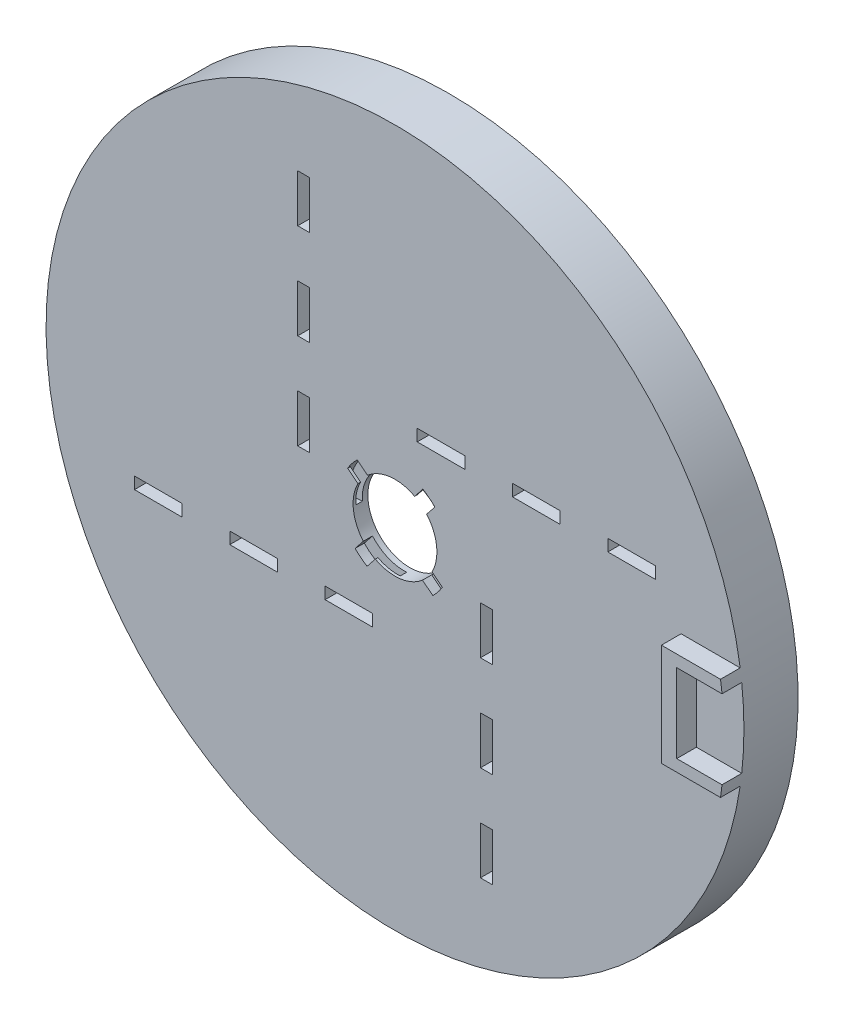
SolidWorks part; units mm, degrees
material "ABS"
ref_plane "Front Plane" through (0, 0, 0) normal (0, 0, 1) x (1, 0, 0)
ref_plane "Top Plane" through (0, 0, 0) normal (0, 1, 0) x (1, 0, 0)
ref_plane "Right Plane" through (0, 0, 0) normal (1, 0, 0) x (0, 0, -1)
sketch "Sketch1" plane through (0, 0, 0) normal (0, 0, 1) x (1, 0, 0)
  line L0 (0, 0) -> (0, -100) construction
  line L1 (-100, -100) -> (100, -100)
  line L2 (-100, -100) -> (-100, 100)
  line L3 (100, -100) -> (100, 100)
  line L4 (100, 100) -> (-100, 100)
  circle A0 centre (0, 0) radius 10.65
  point P7 (0, -100)
  dimension "D1" = 21.3
  dimension "D2" = 100
  dimension "D3" = 200
  dimension "D4" = 200
extrude "Boss-Extrude1" add sketch "Sketch1" against normal blind 3.75
sketch "Sketch2" plane through (0, 0, 0) normal (0, 0, 1) x (1, 0, 0)
  line L0 (0, 0) -> (0, 13.95) construction
  line L1 (0, 10.65) -> (0, 13.95)
  line L2 (8.6829, 10.9183) -> (6.6289, 8.3355)
  line L3 (-0.8501, 13.9241) -> (-0.649, 10.6302)
  circle A0 centre (0, 0) radius 10.65 construction
  circle A1 centre (0, 0) radius 13.95
  circle A2 centre (0, 0) radius 10.65
  arc A3 (0, 12.3) -> (-0.7495, 12.2771) centre (0, 0) ccw construction
  arc A4 (0, 12.3) -> (0.7495, 12.2771) centre (0, 0) cw construction
  arc A5 (0.7495, 12.2771) -> (7.6559, 9.6269) centre (0, 0) cw construction
  arc A6 (0.8501, 13.9241) -> (8.6829, 10.9183) centre (0, 0) cw
  arc A7 (0, 13.95) -> (0.8501, 13.9241) centre (0, 0) cw
  arc A8 (0, 13.95) -> (-0.8501, 13.9241) centre (0, 0) ccw
  arc A9 (0.649, 10.6302) -> (6.6289, 8.3355) centre (0, 0) cw
  arc A10 (0, 10.65) -> (0.649, 10.6302) centre (0, 0) cw
  arc A11 (0, 10.65) -> (-0.649, 10.6302) centre (0, 0) ccw
  dimension "D7" = 21.3
  dimension "D2" = 0.75
  dimension "D3" = 0.75
  dimension "D4" = 35
  dimension "D1" = 3.3
  dimension "D5" = 1.65
  dimension "D6" = 1.65
extrude "Cut-Extrude4" cut sketch "Sketch2" against normal mid plane 1.65 from offset 1.5 contours L2 A9 A10 A11 L3 A8 A7 A6 offset against normal yes
sketch "Sketch4" plane through (0, 0, -2.325) normal (0, 0, 1) x (1, 0, 0)
  line L0 (5.0003, 9.4031) -> (7.0769, 12.0216)
  line L1 (8.0358, 6.9892) -> (10.1194, 9.6021)
  arc A0 (6.6289, 8.3355) -> (8.0358, 6.9892) centre (0, 0) cw
  arc A1 (6.6289, 8.3355) -> (5.0003, 9.4031) centre (0, 0) ccw
  arc A2 (8.6829, 10.9183) -> (7.0769, 12.0216) centre (0, 0) ccw
  arc A3 (8.6829, 10.9183) -> (10.1194, 9.6021) centre (0, 0) cw
  dimension "D1" = 1.95
  dimension "D2" = 1.95
  dimension "D3" = 1.95
  dimension "D4" = 1.95
extrude "Cut-Extrude5" cut sketch "Sketch4" along normal through all
pattern_circular "CirPattern1" count 4 over 360 about axis through (0, 0, 0) along (0, 0, 1) of "Cut-Extrude5", "Cut-Extrude4"
sketch "Sketch5" plane through (0, 0, 0) normal (0, 0, 1) x (1, 0, 0)
  line L0 (0, 0) -> (15, 0)
  line L1 (15, 0) -> (47, 0)
  line L2 (47, 0) -> (15.5, 0)
  line L3 (15.5, 0) -> (5.65, 0)
  line L4 (5.65, 0) -> (5.65, 21.7)
  line L5 (5.65, 21.7) -> (17.75, 21.7)
  line L6 (5.65, 21.7) -> (5.65, 24.7)
  line L7 (17.75, 21.7) -> (17.75, 24.7)
  line L8 (5.65, 24.7) -> (17.75, 24.7)
  line L9 (17.75, 21.7) -> (29.85, 21.7)
  line L10 (29.85, 21.7) -> (29.85, 24.7)
  line L11 (29.85, 21.7) -> (41.95, 21.7)
  line L12 (29.85, 24.7) -> (41.95, 24.7)
  line L13 (41.95, 21.7) -> (41.95, 24.7)
  line L14 (41.95, 21.7) -> (54.05, 21.7)
  line L15 (54.05, 21.7) -> (66.15, 21.7)
  line L16 (54.05, 21.7) -> (54.05, 24.7)
  line L17 (66.15, 21.7) -> (66.15, 24.7)
  line L18 (54.05, 24.7) -> (66.15, 24.7)
  dimension "D1" = 15
  dimension "D2" = 32
  dimension "D3" = 31.5
  dimension "D4" = 9.85
  dimension "D5" = 21.7
  dimension "D6" = 12.1
  dimension "D7" = 3
  dimension "D8" = 12.1
  dimension "D9" = 12.1
  dimension "D10" = 12.1
  dimension "D11" = 12.1
  dimension "D12" = 3
  dimension "D13" = 3
extrude "Cut-Extrude6" cut sketch "Sketch5" against normal blind 10 contours L11 L13 L12 L10 | L18 L16 L15 L17 | L5 L6 L8 L7 region at (60.1, 23.2, 0) region at (35.9, 23.2, 0)
pattern_circular "CirPattern2" count 4 over 360 about axis through (0, 0, -3.75) along (0, 0, 1) of "Cut-Extrude6"
sketch "Sketch6" plane through (0, 0, -3.75) normal (0, 0, -1) x (-1, 0, 0)
  line L0 (100, -100) -> (-100, -100)
  line L1 (100, -100) -> (100, 100.1827)
  line L2 (-100, -100) -> (-100, 100.1827)
  line L3 (100, 100.1827) -> (-100, 100.1827)
  circle A0 centre (0, 0) radius 70.611 construction
  circle A1 centre (0, 0) radius 88.611
  dimension "D1" = 18
extrude "Cut-Extrude7" cut sketch "Sketch6" against normal through all contours L0 L1 L3 L2 | A1
sketch "Sketch8" plane through (0, 0, 0) normal (0, 0, 1) x (1, 0, 0)
  line L0 (0, 0) -> (-80.611, 0)
  line L1 (-88.2738, 7.723) -> (-86.7795, 7.5922)
  line L2 (-88.2738, -7.723) -> (-86.7795, -7.5922)
  circle A0 centre (0, 0) radius 88.611 construction
  circle A1 centre (0, 0) radius 87.111 construction
  circle A2 centre (0, 0) radius 86.111
  circle A3 centre (0, 0) radius 84.611
  arc A5 (-88.2738, 7.723) -> (-88.2738, -7.723) centre (0, 0) cw
  arc A6 (-88.2738, 7.723) -> (-88.2738, -7.723) centre (0, 0) ccw construction
  arc A7 (-86.7795, 7.5922) -> (-86.7795, -7.5922) centre (0, 0) cw
  circle A8 centre (0, 0) radius 88.611 construction
  dimension "D4" = 1.5
  dimension "D1" = 1.5
  dimension "D2" = 1
  dimension "D3" = 1.5
extrude "Boss-Extrude2" add sketch "Sketch8" against normal blind 13.75 contours A0 A1 | A2 A3 | L1 A7 L2 A5 region at (-85.8674, 0, 0)
sketch "Sketch9" plane through (0, 0, 0) normal (0, 0, 1) x (1, 0, 0)
  line L0 (0, 0) -> (88.611, 0)
  line L1 (0, 0) -> (83.2671, 30.3067) construction
  circle A0 centre (0, 0) radius 88.611 construction
  dimension "D1" = 20
ref_plane "Plane1" through (83.2671, 0, 0) normal (1, 0, 0) x (0, 0, -1)
sketch "Sketch10" plane through (83.2671, 0, 0) normal (1, 0, 0) x (0, 0, -1)
  line L0 (0, 30.3067) -> (3.75, 30.3067) construction
  circle A0 centre (1.875, 30.3067) radius 0.825
  dimension "D1" = 3.75
  dimension "D2" = 1.65
sketch "Sketch11" plane through (0, 0, 0) normal (0, 0, 1) x (1, 0, 0)
  line L0 (76.546, -10) -> (88.0449, -10)
  line L1 (76.546, -10) -> (88.0449, -10) construction
  line L2 (76.546, 10) -> (76.546, -10) construction
  line L3 (76.546, -10) -> (76.546, 10)
  line L4 (76.546, 10) -> (88.0449, 10)
  line L5 (88.611, 0) -> (0, 0) construction
  line L6 (106.546, -13) -> (87.6522, -13) construction
  line L7 (87.6522, 13) -> (72.6522, 13)
  line L8 (72.6522, 13) -> (72.6522, -13)
  line L9 (72.6522, -13) -> (87.6522, -13)
  arc A0 (88.0449, -10) -> (87.6522, -13) centre (0, 0) cw
  circle A1 centre (0, 0) radius 88.611 construction
  arc A4 (88.0449, 10) -> (87.6522, 13) centre (0, 0) ccw
  dimension "D1" = 15
extrude "Boss-Extrude3" add sketch "Sketch11" along normal blind 5
equation "\"OuterThickness\"= 3mm"
equation "\"MasterFillet\"= 3mm"
equation "\"PartSeperation\"= 6mm"
equation "\"Tolerance\"= 0.15mm"
equation "\"HeightPart\"= 100mm"
equation "\"Holes\"= 1.5mm"
equation "\"SpineHolderThickness\"= 3mm"
equation "\"SpineHolderDepth\" = 3mm"
equation "\"D1@Sketch1\"= \"SpineDiameter\" + \"SpineHolderThickness\" * 2 + \"Tolerance\" * 2"
equation "\"D3@Sketch1\"=\"HeightPart\"*2"
equation "\"D4@Sketch1\"=\"HeightPart\"*2"
equation "\"D1@Boss-Extrude1\"=\"SpineHolderDepth\"*1.25"
equation "\"D1@Sketch2\"=\"Tolerance\"*2+\"SpineHolderThickness\""
equation "\"D2@Sketch2\"=\"SpineHolderThickness\"/4"
equation "\"D3@Sketch2\"=\"SpineHolderThickness\"/4"
equation "\"D5@Sketch2\"=\"Tolerance\"+\"SpineHolderThickness\"/2"
equation "\"D19@Cut-Extrude4\"=\"SpineHolderDepth\"/2"
equation "\"D1@Cut-Extrude4\"=\"SpineHolderThickness\"/2+\"Tolerance\""
equation "\"D1@Sketch4\"=\"Tolerance\"*3+\"SpineHolderThickness\"/2"
equation "\"D2@Sketch4\"=\"Tolerance\"*3+\"SpineHolderThickness\"/2"
equation "\"D3@Sketch4\"=\"Tolerance\"*3+\"SpineHolderThickness\"/2"
equation "\"D4@Sketch4\"=\"Tolerance\"*3+\"SpineHolderThickness\"/2"
equation "\"D2@Sketch1\"=\"HeightPart\""
equation "\"MotorLength\" = 40.5mm"
equation "\"MotorWidth\" = 20.3mm"
equation "\"AttachmentHeight\"= 3mm"
equation "\"SpoolDiameter\"= 60mm"
equation "\"SpoolHeight\"= 2mm"
equation "\"SpoolRidgeHeight\"= 1mm"
equation "\"SpoolRidgeDepth\"= 2mm"
equation "\"SpoolSeperation\"= 2mm"
equation "\"ServoHolderWidthOffset\"= 20mm"
equation "\"MotorTransmitterToScrew\"= 21.7mm"
equation "\"SpoolToSpine\"= 15mm"
equation "\"D1@Sketch5\"=\"SpoolToSpine\""
equation "\"D2@Sketch5\"=\"SpoolDiameter\"/2+\"SpoolRidgeDepth\""
equation "\"SpoolCenterToMotor\" = 31.5mm"
equation "\"D3@Sketch5\"=\"SpoolCenterToMotor\""
equation "\"D4@Sketch5\"=((\"MotorLength\"+\"ServoHolderWidthOffset\")-(\"MotorLength\"+\"Tolerance\"*2))/2"
equation "\"D5@Sketch5\"=\"MotorTransmitterToScrew\""
equation "\"D6@Sketch5\"=(\"MotorLength\"+\"ServoHolderWidthOffset\")*1/5"
equation "\"D7@Sketch5\"=3"
equation "\"D8@Sketch5\"=(\"MotorLength\"+\"ServoHolderWidthOffset\")*1/5"
equation "\"D9@Sketch5\"=(\"MotorLength\"+\"ServoHolderWidthOffset\")*1/5"
equation "\"D10@Sketch5\"=(\"MotorLength\"+\"ServoHolderWidthOffset\")*1/5"
equation "\"D11@Sketch5\"=(\"MotorLength\"+\"ServoHolderWidthOffset\")*1/5"
equation "\"D12@Sketch5\"=3"
equation "\"D13@Sketch5\"=3"
equation "\"HubOffset\"= 18mm"
equation "\"D1@Sketch6\"=\"HubOffset\""
equation "\"D1@Boss-Extrude2\"=\"SpineHolderDepth\"*1.25+10.00mm"
equation "\"D1@Sketch10\"=\"SpineHolderDepth\"*1.25"
equation "\"D2@Sketch10\"=\"SpineHolderDepth\"/2 +\"Tolerance\""
equation "\"D6@Sketch2\"=\"Tolerance\"+\"SpineHolderThickness\"/2"
equation "\"D7@Sketch2\" = \"SpineDiameter\" + \"SpineHolderThickness\" * 2 + \"Tolerance\" * 2"
equation "\"DiscThickness\"= 4mm"
equation "\"LigamentThickness\"= 2mm"
equation "\"LigamentExtension\"= 1mm"
equation "\"LigamentAngle\"= 20deg"
equation "\"SpineDiameter\"= 15mm"
equation "\"LigamentDepth\"= 1mm"
equation "\"ServoFastenerHolders\"=2mm"
equation "\"ArduinoLength\" = 53.4mm"
equation "\"ArduinoWidth\" = 50mm"
equation "\"ArdYOffset\" = 29.5mm"
equation "\"ArdXOffset\" = 20.5mm"
equation "\"ArdXOffsetSmall\" = 25mm"
equation "\"MiddleServoOffset\"= 12mm"
equation "\"LargeServoOffset\"= 3mm"
equation "\"SmallServoOffset\"= 0mm"
equation "\"ToolHoleDiameter\"= 12mm"
